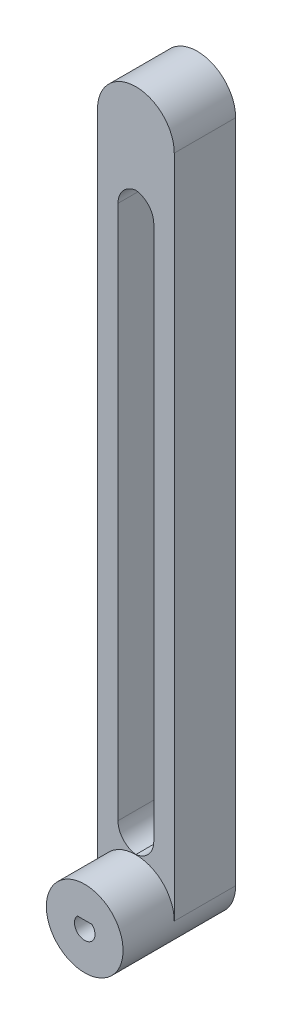
SolidWorks part; units mm, degrees
ref_plane "Front Plane" through (0, 0, 0) normal (0, 0, 1) x (1, 0, 0)
ref_plane "Top Plane" through (0, 0, 0) normal (0, 1, 0) x (1, 0, 0)
ref_plane "Right Plane" through (0, 0, 0) normal (1, 0, 0) x (0, 0, -1)
sketch "Sketch1" plane through (0, 0, 0) normal (0, 0, 1) x (1, 0, 0)
  line L0 (-5.6452, 102.5806) -> (-5.6452, -27.4194)
  line L1 (9.3548, 102.5806) -> (9.3548, -27.4194)
  arc A0 (-5.6452, 102.5806) -> (9.3548, 102.5806) centre (1.8548, 102.5806) cw
  arc A1 (-5.6452, -27.4194) -> (9.3548, -27.4194) centre (1.8548, -27.4194) ccw
  dimension "D1" = 15
  dimension "D2" = 130
extrude "Boss-Extrude1" add sketch "Sketch1" along normal blind 12
sketch "Sketch2" plane through (0, 0, 12) normal (0, 0, 1) x (1, 0, 0)
  line L0 (-5.6452, -27.4194) -> (9.3548, -27.4194) construction
  circle A0 centre (1.8548, -27.4194) radius 3.1
extrude "Boss-Extrude2" add sketch "Sketch2" along normal blind 15
sketch "Sketch3" plane through (0, 0, 27) normal (0, 0, 1) x (1, 0, 0)
  line L0 (0.1666, -24.8194) -> (3.543, -24.8194)
  circle A0 centre (1.8548, -27.4194) radius 3.1 construction
  circle A1 centre (1.8548, -27.4194) radius 3.1 construction
  arc A2 (0.1666, -24.8194) -> (3.543, -24.8194) centre (1.8548, -27.4194) ccw
  dimension "3.6" = 2.6
extrude "Cut-Extrude1" cut sketch "Sketch3" against normal blind 50
sketch "Sketch4" plane through (0, 0, 27) normal (0, 0, 1) x (1, 0, 0)
  line L0 (0.1666, -24.8194) -> (3.543, -24.8194)
  arc A0 (0.1666, -24.8194) -> (3.543, -24.8194) centre (1.8548, -27.4194) cw
extrude "Cut-Extrude2" cut sketch "Sketch4" against normal blind 15
sketch "Sketch5" plane through (0, 0, 12) normal (0, 0, 1) x (1, 0, 0)
  line L0 (-5.6452, 102.5806) -> (-5.6452, -27.4194) construction
  line L1 (-1.6452, -19.9194) -> (-5.6452, -19.9194) construction
  line L2 (-1.6452, -19.9194) -> (-1.6452, 92.5806) construction
  line L3 (-1.6452, 92.5806) -> (-5.6452, 92.5806) construction
  line L4 (-5.6452, -19.9194) -> (-5.6452, 92.5806) construction
  line L6 (5.3548, -19.9194) -> (9.3548, -19.9194) construction
  line L7 (5.3548, -19.9194) -> (5.3548, 92.5806) construction
  line L8 (5.3548, 92.5806) -> (9.3548, 92.5806) construction
  line L9 (9.3548, -19.9194) -> (9.3548, 92.5806) construction
  line L10 (-1.6452, 92.5806) -> (5.3548, 92.5806)
  line L11 (-1.6452, 92.5806) -> (-1.6452, -19.9194)
  line L12 (-1.6452, -19.9194) -> (5.3548, -19.9194)
  line L13 (5.3548, 92.5806) -> (5.3548, -19.9194)
  arc A0 (-5.6452, -27.4194) -> (9.3548, -27.4194) centre (1.8548, -27.4194) cw construction
  arc A1 (9.3548, 102.5806) -> (-5.6452, 102.5806) centre (1.8548, 102.5806) ccw construction
  dimension "D1" = 4
  dimension "D2" = 4
  dimension "D3" = 10
extrude "Cut-Extrude3" cut sketch "Sketch5" against normal blind 12
sketch "Sketch6" plane through (-5.6452, 0, 0) normal (-1, 0, 0) x (0, 0, 1)
  line L0 (6, 102.5806) -> (6, 14.8619) construction
  line L1 (12, 102.5806) -> (0, 102.5806) construction
  circle A0 centre (6, 78.769) radius 5.15
  circle A1 centre (6, 53.769) radius 5.15
  circle A2 centre (6, 28.769) radius 5.15
  dimension "D1" = 3
extrude "Cut-Extrude4" cut sketch "Sketch6" against normal blind 2
fillet "Fillet1" radius 4 4 edges at (-1.6452, -19.9194, 6) (5.3548, -19.9194, 6) (5.3548, 92.5806, 6) (-1.6452, 92.5806, 6)
sketch "Sketch7" plane through (0, 0, 12) normal (0, 0, 1) x (1, 0, 0)
  arc A0 (-5.6452, -27.4194) -> (9.3548, -27.4194) centre (1.8548, -27.4194) ccw
  arc A1 (-5.6452, -27.4194) -> (9.3548, -27.4194) centre (1.8548, -27.4194) ccw construction
  arc A2 (-5.6452, -27.4194) -> (9.3548, -27.4194) centre (1.8548, -27.4194) cw
extrude "Boss-Extrude3" add sketch "Sketch7" along normal blind 10
sketch "Sketch9" plane through (0, 0, 22) normal (0, 0, 1) x (1, 0, 0)
  circle A0 centre (1.8548, -27.4194) radius 2.1
extrude "Cut-Extrude5" cut sketch "Sketch9" against normal blind 7
sketch "Sketch10" plane through (0, 0, 22) normal (0, 0, 1) x (1, 0, 0)
  line L0 (0.694, -25.6694) -> (3.0157, -25.6694)
  line L1 (1.8548, -29.5194) -> (1.8548, -27.4194) construction
  circle A0 centre (1.8548, -27.4194) radius 2.1 construction
  circle A1 centre (1.8548, -27.4194) radius 2.1 construction
  arc A2 (0.694, -25.6694) -> (3.0157, -25.6694) centre (1.8548, -27.4194) cw
  dimension "D1" = 1.75
extrude "Boss-Extrude4" add sketch "Sketch10" against normal blind 7
sketch "Sketch11" plane through (0, 0, 22) normal (0, 0, 1) x (1, 0, 0)
  line L1 (0.1462, -25.9133) -> (3.5376, -25.9133)
  line L2 (0.1462, -25.9133) -> (0.1462, -25.4168)
  line L3 (0.1462, -25.4168) -> (3.5376, -25.4168)
  line L4 (3.5376, -25.9133) -> (3.5376, -25.4168)
extrude "Boss-Extrude7" add sketch "Sketch11" against normal blind 7
sketch "Sketch12" plane through (0, 0, 22) normal (0, 0, 1) x (1, 0, 0)
  line L2 (0.3913, -25.9133) -> (3.3183, -25.9133) construction
  line L3 (3.2813, -26.0033) -> (0.4283, -26.0033)
  line L4 (3.2813, -26.0033) -> (0.4283, -26.0033)
  line L5 (0.3913, -25.9133) -> (3.3183, -25.9133)
  arc A1 (0.3913, -25.9133) -> (3.3183, -25.9133) centre (1.8548, -27.4194) ccw construction
  arc A2 (0.4283, -26.0033) -> (3.2813, -26.0033) centre (1.8548, -27.4194) ccw
  arc A3 (0.4283, -26.0033) -> (3.2813, -26.0033) centre (1.8548, -27.4194) ccw
  arc A4 (0.3913, -25.9133) -> (3.3183, -25.9133) centre (1.8548, -27.4194) ccw
  dimension "D1" = 0.09
extrude "Boss-Extrude8" add sketch "Sketch12" against normal blind 10
